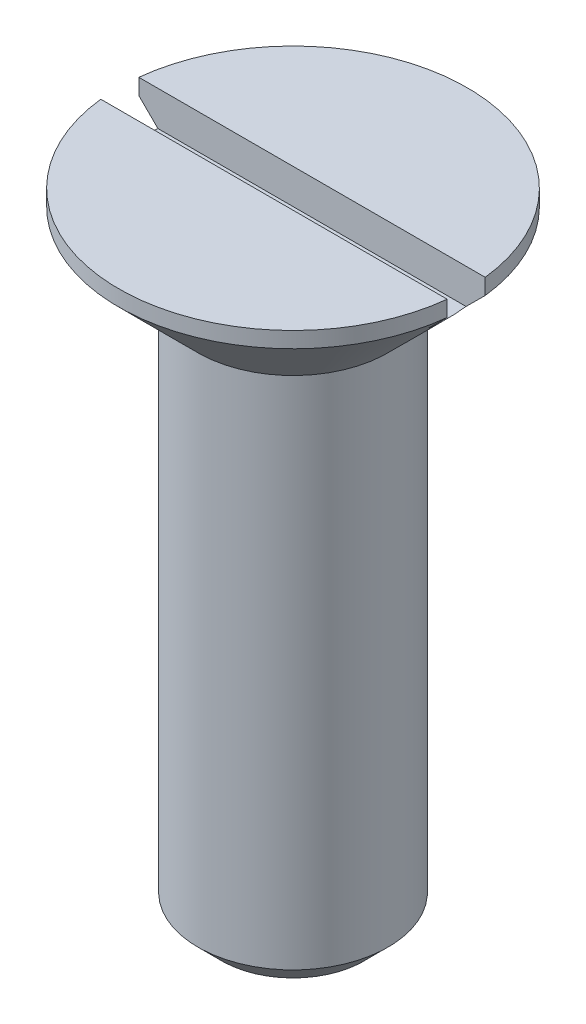
SolidWorks part; units mm, degrees
ref_plane "Спереди" through (0, 0, 0) normal (0, 0, 1) x (1, 0, 0)
ref_plane "Сверху" through (0, 0, 0) normal (0, 1, 0) x (1, 0, 0)
ref_plane "Справа" through (0, 0, 0) normal (1, 0, 0) x (0, 0, -1)
sketch "Эскиз1" plane through (0, 0, 0) normal (0, 0, 1) x (1, 0, 0)
  line L0 (0, 125.7632) -> (0, 0) construction
  line L2 (0, 20) -> (0, 0)
  line L3 (0, 20) -> (5.5, 20)
  line L4 (3, 17) -> (3, 0)
  line L5 (3, 17) -> (5.5, 19.5)
  line L6 (3, 0) -> (0, 0)
  line L7 (5.5, 20) -> (5.5, 19.5)
  dimension "D1" = 5.5
  dimension "D2" = 20
  dimension "D3" = 3
  dimension "D4" = 45
  dimension "D5" = 3
revolve "Повернуть1" add sketch "Эскиз1" angle 360 about L0
ref_axis "Ось4" through (0, 18.7854, 0) along (0, -1, 0)
sketch "Эскиз13" plane through (0, 20, 0) normal (0, 1, 0) x (-1, 0, 0)
  line L1 (6, -0.6) -> (-6, -0.6)
  line L2 (6, -0.6) -> (6, 0.6)
  line L3 (6, 0.6) -> (-6, 0.6)
  line L4 (-6, -0.6) -> (-6, 0.6)
  dimension "D1" = 6
  dimension "D2" = 12
  dimension "D3" = 0.6
  dimension "D4" = 1.2
extrude "Вырез-Вытянуть9" cut sketch "Эскиз13" against normal blind 1.1
chamfer "Фаска1" distance 0.75 angle 45 1 edges at (-3, 0, 0)
